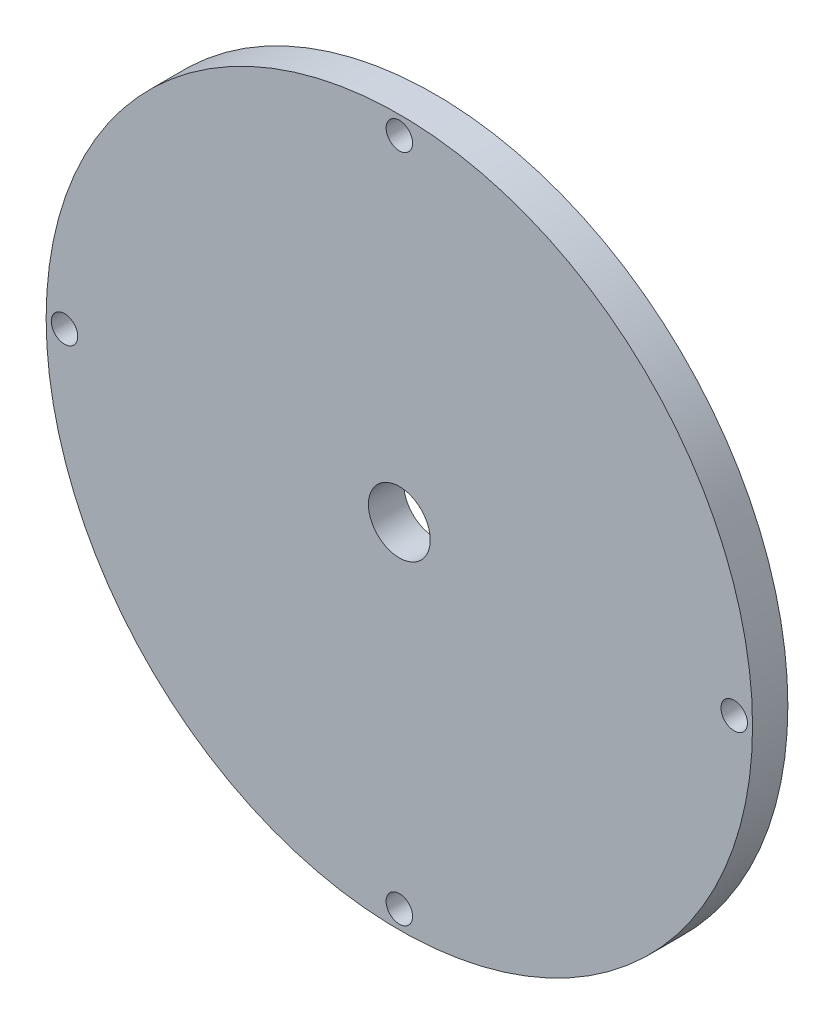
SolidWorks part; units mm, degrees
material "6061 Alloy"
ref_plane "Front Plane" through (0, 0, 0) normal (0, 0, 1) x (1, 0, 0)
ref_plane "Top Plane" through (0, 0, 0) normal (0, 1, 0) x (1, 0, 0)
ref_plane "Right Plane" through (0, 0, 0) normal (1, 0, 0) x (0, 0, -1)
sketch "Sketch1" plane through (0, 0, 0) normal (0, 0, 1) x (1, 0, 0)
  circle A0 centre (0, 0) radius 63.5
extrude "Boss-Extrude1" add sketch "Sketch1" along normal blind 6.35
sketch "Sketch2" plane through (0, 0, 0) normal (0, 0, -1) x (-1, 0, 0)
  circle A0 centre (0, 0) radius 50.8
  circle A1 centre (0, 0) radius 57.15
extrude "Cut-Extrude1" cut sketch "Sketch2" against normal blind 1.27
sketch "Sketch4" plane through (0, 0, 0) normal (0, 0, -1) x (-1, 0, 0)
  circle A0 centre (0, 60.198) radius 2.3812
  circle A1 centre (60.198, 0) radius 2.3812
  circle A2 centre (0, -60.198) radius 2.3812
  circle A3 centre (-60.198, 0) radius 2.3812
  point P12 (0, 0)
  dimension "D1" = 60.198
  dimension "D2" = 4
extrude "Cut-Extrude2" cut sketch "Sketch4" against normal through all
sketch "Sketch6" plane through (0, 0, 0) normal (0, 0, -1) x (-1, 0, 0)
  circle A0 centre (0, 0) radius 5.5562
extrude "Cut-Extrude4" cut sketch "Sketch6" against normal through all
